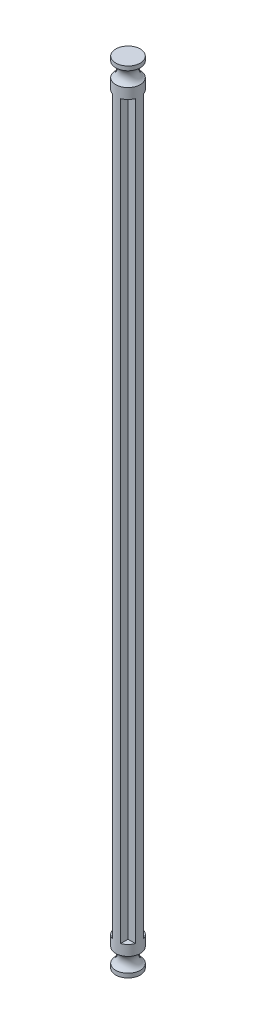
SolidWorks part; units mm, degrees
ref_plane "前视基准面" through (0, 0, 0) normal (0, 0, 1) x (1, 0, 0)
ref_plane "上视基准面" through (0, 0, 0) normal (0, 1, 0) x (1, 0, 0)
ref_plane "右视基准面" through (0, 0, 0) normal (1, 0, 0) x (0, 0, -1)
sketch "草图1" plane through (0, 0, 0) normal (0, 1, 0) x (1, 0, 0)
  line L0 (1, 1) -> (1, 2.7753)
  line L7 (1, 1) -> (2.7753, 1)
  line L8 (1, -1) -> (2.7753, -1)
  line L9 (1, -1) -> (1, -2.7753)
  line L10 (-1, -1) -> (-1, -2.7753)
  line L11 (-1, -1) -> (-2.7753, -1)
  line L12 (-1, 1) -> (-2.7753, 1)
  line L13 (-1, 1) -> (-1, 2.7753)
  arc A0 (-2.7753, 1) -> (-2.7753, -1) centre (0, 0) ccw
  arc A1 (-1, -2.7753) -> (1, -2.7753) centre (0, 0) ccw
  arc A2 (2.7753, -1) -> (2.7753, 1) centre (0, 0) ccw
  arc A3 (1, 2.7753) -> (-1, 2.7753) centre (0, 0) ccw
  dimension "D1" = 5.9
  dimension "D2" = 2
  dimension "D3" = 2
  dimension "D4" = 2
  dimension "D5" = 2
  dimension "D6" = 1
  dimension "D7" = 1
  dimension "D8" = 1
  dimension "D9" = 1
extrude "凸台-拉伸2" add sketch "草图1" along normal blind 176.23
sketch "草图3" plane through (0, 0, 0) normal (1, 0, 0) x (0, 0, -1)
  line L0 (0, 176.23) -> (0, 183.23)
  line L1 (1, 176.23) -> (-1, 176.23) construction
  line L2 (0, 183.23) -> (2.95, 183.23)
  line L3 (0, 176.23) -> (2.95, 176.23)
  line L4 (2.95, 176.23) -> (2.95, 178.73)
  line L5 (2.95, 183.23) -> (2.95, 182.23)
  line L6 (0, 0) -> (0, -7)
  line L7 (0, -7) -> (2.95, -7)
  line L8 (0, 0) -> (2.95, 0)
  line L9 (2.95, 0) -> (2.95, -2.5)
  line L10 (2.95, -7) -> (2.95, -6)
  arc A0 (2.95, 182.23) -> (2.95, 178.73) centre (3.9182, 180.48) ccw
  arc A1 (2.95, -2.5) -> (2.95, -6) centre (3.9182, -4.25) ccw
  dimension "D5" = 1
  dimension "D4" = 2
  dimension "D9" = 2
  dimension "D1" = 2.95
  dimension "D2" = 7
  dimension "D3" = 2.5
  dimension "D6" = 7
  dimension "D7" = 2.5
  dimension "D8" = 1
revolve "旋转3" add sketch "草图3" angle 360 about L6
